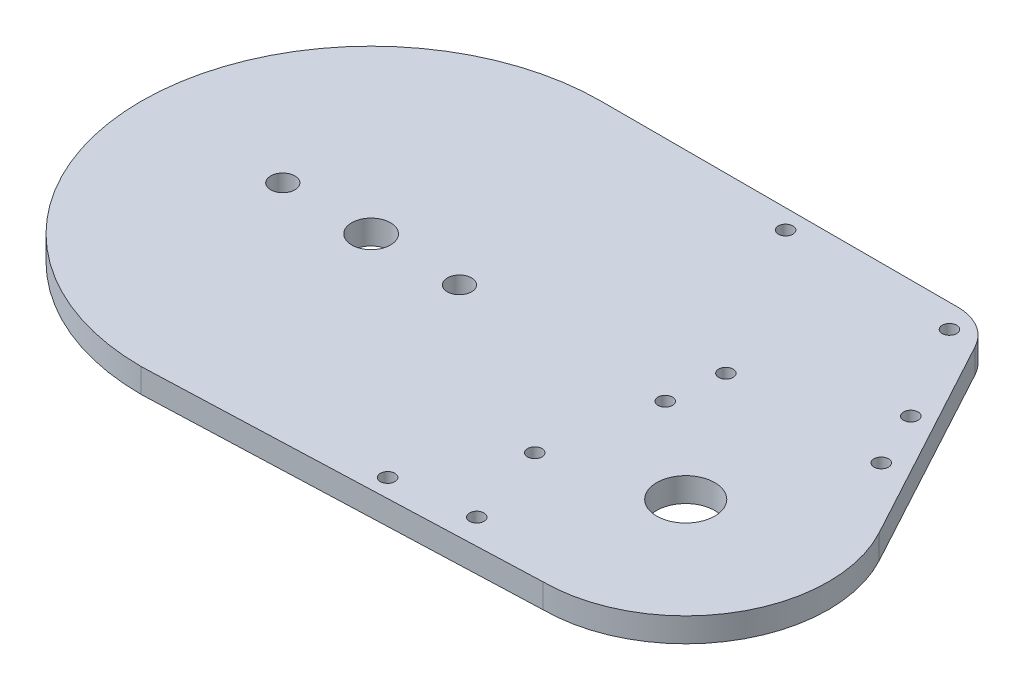
SolidWorks part; units mm, degrees
ref_plane "前视基准面" through (0, 0, 0) normal (0, 0, 1) x (1, 0, 0)
ref_plane "上视基准面" through (0, 0, 0) normal (0, 1, 0) x (1, 0, 0)
ref_plane "右视基准面" through (0, 0, 0) normal (1, 0, 0) x (0, 0, -1)
sketch "Sketch1" plane through (0, 0, 0) normal (0, 1, 0) x (1, 0, 0)
  line L0 (0, 0) -> (0, -15) construction
  line L1 (0, -15) -> (80, -15) construction
  line L2 (0, -47.5) -> (0, -44.5) construction
  line L3 (0, -44.5) -> (94.3585, -44.5) construction
  line L4 (0, -47.5) -> (80, -44.5)
  line L5 (0, 47.5) -> (73.764, 47.5)
  line L6 (82.559, 42.259) -> (105.9453, -0.9611)
  line L7 (0, 0) -> (80, -15) construction
  line L8 (80, -15) -> (60.3319, 0.4326) construction
  line L9 (78.1615, 44.8795) -> (78.8831, 46.0904) construction
  line L10 (78.8831, 46.0904) -> (76.8355, 42.6542) construction
  line L11 (73.764, 47.5) -> (82.559, 42.259) construction
  line L12 (78.1615, 44.8795) -> (73.764, 37.5) construction
  arc A0 (0, 47.5) -> (0, -47.5) centre (0, 0) ccw
  arc A2 (80, -44.5) -> (105.9453, -0.9611) centre (80, -15) ccw
  circle A3 centre (75.0001, 47.5) radius 7.5 construction
  arc A4 (82.559, 42.259) -> (73.764, 47.5) centre (73.764, 37.5) ccw
  circle A5 centre (0, 0) radius 4
  circle A12 centre (80, -15) radius 25 construction
  circle A15 centre (60.3319, 0.4326) radius 1.5
  circle A17 centre (0, 0) radius 18.25 construction
  circle A18 centre (18.25, 0) radius 2.5
  circle A19 centre (-18.25, 0) radius 2.5
  circle A20 centre (80, -15) radius 6
  circle A21 centre (76.8355, 42.6542) radius 1.5
  circle A22 centre (88.3547, 23.1429) radius 1.5
  circle A23 centre (42.1373, 43.5) radius 1.5
  circle A24 centre (45.2934, -41.8851) radius 1.5
  circle A25 centre (61.5917, 11.711) radius 1.5
  circle A26 centre (93.688, 11.711) radius 1.5
  circle A27 centre (61.5917, -39.7686) radius 1.5
  circle A29 centre (56.0772, -22.2593) radius 1.5
  point P28 (75, -15)
  dimension "D1" = 95
  dimension "D4" = 27.5
  dimension "D6" = 15
  dimension "D7" = 10
  dimension "D8" = 8
  dimension "D9" = 50
  dimension "D10" = 3
  dimension "D12" = 4
  dimension "D11" = 36.5
  dimension "D13" = 5
  dimension "D14" = 5
  dimension "D15" = 12
  dimension "D16" = 3
  dimension "D17" = 3
  dimension "D18" = 3
  dimension "D19" = 3
  dimension "D20" = 3
  dimension "D21" = 3
  dimension "D22" = 3
  dimension "D2" = 15
  dimension "D3" = 80
  dimension "D5" = 3
extrude "Boss-Extrude1" add sketch "Sketch1" along normal blind 5
